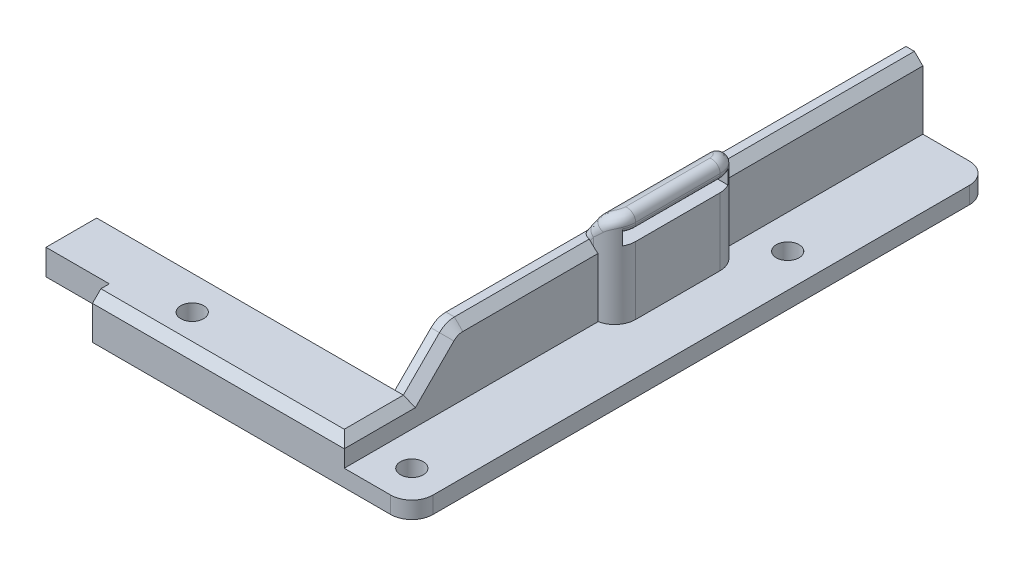
SolidWorks part; units mm, degrees
ref_plane "Front Plane" through (0, 0, 0) normal (0, 0, 1) x (1, 0, 0)
ref_plane "Top Plane" through (0, 0, 0) normal (0, 1, 0) x (1, 0, 0)
ref_plane "Right Plane" through (0, 0, 0) normal (1, 0, 0) x (0, 0, -1)
sketch "Sketch1" plane through (0, 0, 0) normal (0, 1, 0) x (1, 0, 0)
  line L0 (204.7875, -25.4) -> (204.7875, 148.59)
  line L1 (0, 0) -> (179.3875, 0)
  line L2 (0, 0) -> (0, 148.59)
  line L3 (-25.4, -25.4) -> (204.7875, -25.4)
  line L4 (179.3875, 0) -> (179.3875, 148.59)
  line L5 (-25.4, -25.4) -> (-25.4, 148.59)
  line L6 (204.7875, 148.59) -> (179.3875, 148.59)
  line L7 (0, 148.59) -> (-25.4, 148.59)
  dimension "D1" = 179.3875
  dimension "D2" = 148.59
  dimension "D3" = 148.59
  dimension "D4" = 25.4
extrude "Boss-Extrude1" add sketch "Sketch1" along normal blind 5.08
sketch "Sketch2" plane through (0, 5.08, 0) normal (0, 1, 0) x (1, 0, 0)
  line L6 (184.4675, 148.59) -> (179.3875, 148.59)
  line L7 (179.3875, 148.59) -> (179.3875, 0)
  line L8 (179.3875, 0) -> (0, 0)
  line L9 (184.4675, 148.59) -> (184.4675, -5.08)
  line L10 (184.4675, -5.08) -> (-5.08, -5.08)
  line L11 (-5.08, -5.08) -> (-5.08, 148.59)
  line L12 (184.4675, 148.59) -> (184.4675, -5.08)
  line L13 (184.4675, -5.08) -> (-5.08, -5.08)
  line L14 (-5.08, -5.08) -> (-5.08, 148.59)
  line L15 (0, 0) -> (0, 148.59)
  line L16 (0, 148.59) -> (-5.08, 148.59)
  dimension "D1" = 5.08
extrude "Boss-Extrude2" add sketch "Sketch2" along normal blind 20.32
fillet "Fillet1" radius 6.35 4 edges at (204.7875, 2.54, -148.59) (204.7875, 2.54, 25.4) (-25.4, 2.54, 25.4) (-25.4, 2.54, -148.59)
sketch "Sketch3" plane through (0, 5.08, 0) normal (0, 1, 0) x (1, 0, 0)
  line L0 (-5.08, 148.59) -> (-5.08, -5.08) construction
  line L1 (-5.08, 88.9) -> (-10.16, 88.9)
  line L2 (-5.08, 88.9) -> (-5.08, 50.8)
  line L3 (-5.08, 50.8) -> (-10.16, 50.8)
  line L4 (-10.16, 88.9) -> (-10.16, 50.8)
  line L5 (184.4675, -5.08) -> (184.4675, 148.59) construction
  line L6 (184.4675, 50.8) -> (189.5475, 50.8)
  line L7 (184.4675, 50.8) -> (184.4675, 88.9)
  line L8 (184.4675, 88.9) -> (189.5475, 88.9)
  line L9 (189.5475, 50.8) -> (189.5475, 88.9)
  line L10 (-19.05, -25.4) -> (198.4375, -25.4) construction
  dimension "D1" = 38.1
  dimension "D2" = 38.1
  dimension "D3" = 76.2
  dimension "D4" = 76.2
  dimension "D5" = 5.08
  dimension "D6" = 5.08
extrude "Boss-Extrude3" add sketch "Sketch3" along normal blind 27.94
sketch "Sketch4" plane through (0, 0, -88.9) normal (0, 0, -1) x (-1, 0, 0)
  line L0 (-184.4675, 33.02) -> (-179.3875, 25.4)
  line L1 (-179.3875, 25.4) -> (-184.4675, 25.4)
  line L2 (-184.4675, 25.4) -> (-184.4675, 33.02)
  line L3 (5.08, 33.02) -> (0, 25.4)
  line L4 (5.08, 25.4) -> (-184.4675, 25.4) construction
  line L5 (-179.3875, 25.4) -> (0, 25.4) construction
  line L6 (0, 25.4) -> (5.08, 25.4)
  line L7 (5.08, 25.4) -> (5.08, 33.02)
extrude "Boss-Extrude4" add sketch "Sketch4" against normal up to surface (38.1 mm away) up to face at (-7.112, 20.32, -50.8)
sketch "Sketch5" plane through (189.5475, 0, 0) normal (1, 0, 0) x (0, 0, -1)
  line L0 (-5.08, 25.4) -> (50.8, 25.4) construction
  line L1 (53.975, 25.4) -> (85.725, 25.4)
  line L2 (53.975, 25.4) -> (53.975, 28.575)
  line L3 (53.975, 28.575) -> (85.725, 28.575)
  line L4 (85.725, 25.4) -> (85.725, 28.575)
  line L5 (50.8, 33.02) -> (50.8, 5.08) construction
  dimension "D1" = 0
  dimension "D2" = 3.175
  dimension "D3" = 31.75
  dimension "D4" = 3.175
extrude "Cut-Extrude1" cut sketch "Sketch5" against normal through all both and the other way through all
sketch "Sketch6" plane through (0, 0, 0) normal (0, 0, -1) x (-1, 0, 0)
  line L0 (0, 25.4) -> (0, 0) construction
  line L1 (-179.3875, 25.4) -> (0, 25.4)
  line L2 (-179.3875, 25.4) -> (-179.3875, 12.7)
  line L3 (-179.3875, 12.7) -> (0, 12.7)
  line L4 (0, 25.4) -> (0, 12.7)
extrude "Cut-Extrude2" cut sketch "Sketch6" against normal through all
sketch "Sketch8" plane through (179.3875, 0, 0) normal (-1, 0, 0) x (0, 0, 1)
  line L0 (5.08, 12.7) -> (0, 7.62)
  line L1 (0, 7.62) -> (0, 12.7)
  line L2 (0, 12.7) -> (5.08, 12.7)
extrude "Cut-Extrude3" cut sketch "Sketch8" along normal up to surface (179.3875 mm away) up to face at (0, 17.78, -56.642)
sketch "Sketch9" plane through (184.4675, 0, 0) normal (1, 0, 0) x (0, 0, -1)
  line L0 (-5.08, 12.7) -> (7.62, 25.4)
  line L1 (-5.08, 25.4) -> (50.8, 25.4) construction
  line L2 (7.62, 25.4) -> (-5.08, 25.4)
  line L3 (-5.08, 25.4) -> (-5.08, 12.7)
  dimension "D1" = 45
extrude "Cut-Extrude4" cut sketch "Sketch9" against normal through all both and the other way through all
fillet "Fillet3" radius 6.35 1 edges at (89.6938, 7.62, 0)
fillet "Fillet4" radius 6.35 8 edges at (-10.16, 19.05, -88.9) (-10.16, 19.05, -50.8) (189.5475, 19.05, -88.9) (189.5475, 19.05, -50.8) (-5.08, 33.02, -69.85) (184.4675, 33.02, -69.85) (-2.54, 25.4, -7.62) (181.9275, 25.4, -7.62)
fillet "Fillet5" radius 1.27 8 edges at (-2.1167, 28.575, -69.85) (181.5042, 28.575, -69.85) (189.3311, 28.575, -55.5065) (189.3311, 28.575, -84.1935) (-9.9436, 28.575, -84.1935) (-9.9436, 28.575, -55.5065) (189.5475, 28.575, -69.85) (-10.16, 28.575, -69.85)
sketch "Sketch10" plane through (-5.08, 0, 0) normal (-1, 0, 0) x (0, 0, 1)
  line L1 (5.08, 12.7) -> (25.4, 12.7)
  line L2 (5.08, 12.7) -> (5.08, 5.08)
  line L3 (5.08, 5.08) -> (25.4, 5.08)
  line L4 (25.4, 12.7) -> (25.4, 5.08)
extrude "Boss-Extrude5" add sketch "Sketch10" against normal up to surface (189.5475 mm away) up to face at (184.4675, 16.2744, -13.253)
chamfer "Chamfer1" distance 2.54 angle 45 1 edges at (89.6938, 12.7, 25.4)
chamfer "Chamfer2" distance 2.54 angle 45 9 edges at (184.4675, 25.4, -118.6809) (184.4675, 25.4, -30.5893) (184.4675, 24.9166, -7.8202) (184.4675, 18.1201, -0.3401) (184.4675, 12.7, 13.97) (-5.08, 12.7, 13.97) (-5.08, 25.4, -118.6809) (-5.08, 24.9166, -7.8202) (-5.08, 18.1201, -0.3401)
fillet "Fillet8" radius 2.54 14 edges at (-1.5974, 27.7962, -88.9) (-3.4871, 30.5955, -88.9) (-5.1252, 32.0624, -88.7623) (-9.7247, 33.02, -84.8606) (-1.5974, 27.7962, -50.8) (-3.4871, 30.5955, -50.8) (-5.1252, 32.0624, -50.9377) (180.9849, 27.7962, -50.8) (182.8746, 30.5955, -50.8) (184.5127, 32.0624, -50.9377) (189.1122, 33.02, -54.8394) (180.9849, 27.7962, -88.9) (182.8746, 30.5955, -88.9) (184.5127, 32.0624, -88.7623)
sketch "Sketch11" plane through (0, 5.08, 0) normal (0, 1, 0) x (1, 0, 0)
  line L0 (-25.4, 142.24) -> (-25.4, -19.05) construction
  line L1 (204.7875, -19.05) -> (204.7875, 142.24) construction
  line L2 (-5.08, 148.59) -> (-19.05, 148.59) construction
  line L4 (198.4375, 148.59) -> (184.4675, 148.59) construction
  line L5 (184.4675, -25.4) -> (198.4375, -25.4) construction
  line L6 (-19.05, -25.4) -> (-5.08, -25.4) construction
  line L7 (184.4675, -25.4) -> (-5.08, -25.4) construction
  circle A0 centre (-15.24, -15.24) radius 3.429
  circle A1 centre (194.6275, -15.24) radius 3.429
  circle A2 centre (194.6275, 97.79) radius 3.429
  circle A3 centre (-15.24, 97.79) radius 3.429
  circle A4 centre (50.8, -15.24) radius 3.429
  circle A5 centre (128.5875, -15.24) radius 3.429
  dimension "D1" = 6.858
  dimension "D2" = 6.858
  dimension "D3" = 6.858
  dimension "D4" = 6.858
  dimension "D15" = 6.858
  dimension "D16" = 6.858
  dimension "D5" = 10.16
  dimension "D6" = 10.16
  dimension "D7" = 10.16
  dimension "D8" = 10.16
  dimension "D9" = 50.8
  dimension "D10" = 50.8
  dimension "D11" = 10.16
  dimension "D12" = 10.16
  dimension "D13" = 10.16
  dimension "D14" = 10.16
  dimension "D17" = 76.2
  dimension "D18" = 76.2
extrude "Cut-Extrude5" cut sketch "Sketch11" against normal through all both and the other way through all
sketch "Sketch12" plane through (0, 12.7, 0) normal (0, 1, 0) x (1, 0, 0)
  line L0 (89.6937, -22.86) -> (89.6938, 0) construction
  line L1 (-2.54, -22.86) -> (181.9275, -22.86) construction
  line L2 (0, 0) -> (179.3875, 0) construction
  line L3 (89.6938, 0) -> (89.6938, -25.4) construction
  line L4 (184.4675, -25.4) -> (-5.08, -25.4) construction
  line L5 (89.6938, -25.4) -> (89.6938, 157.9407)
  line L6 (89.6938, 157.9407) -> (229.6045, 157.9407)
  line L7 (229.6045, 157.9407) -> (229.6045, -37.244)
  line L8 (229.6045, -37.244) -> (-47.4458, -37.244)
  line L9 (-47.4458, -37.244) -> (-47.4458, 157.9407)
  line L10 (-47.4458, 157.9407) -> (89.6938, 157.9407)
  line L11 (89.6938, -25.4) -> (89.6938, -37.244)
  circle M2 centre (50.8, -15.24) radius 3.429
  line M3 (-2.54, -22.86) -> (181.9275, -22.86)
  line M6 (179.3875, -5.08) -> (0, -5.08)
  line M7 (0, -5.08) -> (-2.54, -5.08)
  line M8 (-2.54, -5.08) -> (-2.54, -22.86)
extrude "Cut-Extrude7" cut sketch "Sketch12" against normal through all both and the other way through all contours L5 M3 M6 M7 M8 M2 | L11 L5 L10 L9 L8 M3 M8 M7 M6 region at (19.6586, 12.7, -65.1987) region at (43.4104, 12.7, 13.9407)
sketch "Sketch13" plane through (89.6938, 0, 0) normal (-1, 0, 0) x (0, 0, 1)
  line L0 (22.86, 12.7) -> (5.08, 12.7) construction
  line L1 (0, 4.9897) -> (20.32, 4.9897)
  line L2 (0, 4.9897) -> (0, 0)
  line L3 (0, 0) -> (25.4, 0)
  line L4 (25.4, 4.9897) -> (25.4, 0)
  line L5 (25.4, 0) -> (20.32, 0)
  line L6 (25.4, 0) -> (25.4, 10.16)
  line L7 (22.86, 12.7) -> (20.32, 12.7)
  line L8 (20.32, 4.9897) -> (20.32, 12.7)
  line L9 (22.86, 12.7) -> (25.4, 10.16)
  line M5 (0, 0) -> (25.4, 0)
  line M6 (25.4, 0) -> (25.4, 10.16)
  line M7 (25.4, 10.16) -> (22.86, 12.7)
  line M8 (22.86, 12.7) -> (5.08, 12.7)
  line M11 (0, 4.9897) -> (0, 0)
  dimension "D1" = 5.08
  dimension "D2" = 135
extrude "Cut-Extrude8" cut sketch "Sketch13" against normal blind 19.05 contours L8 L1 L3 M11 M5 M6 M7 M8 region at (89.6938, 3.8382, 14.9111)
